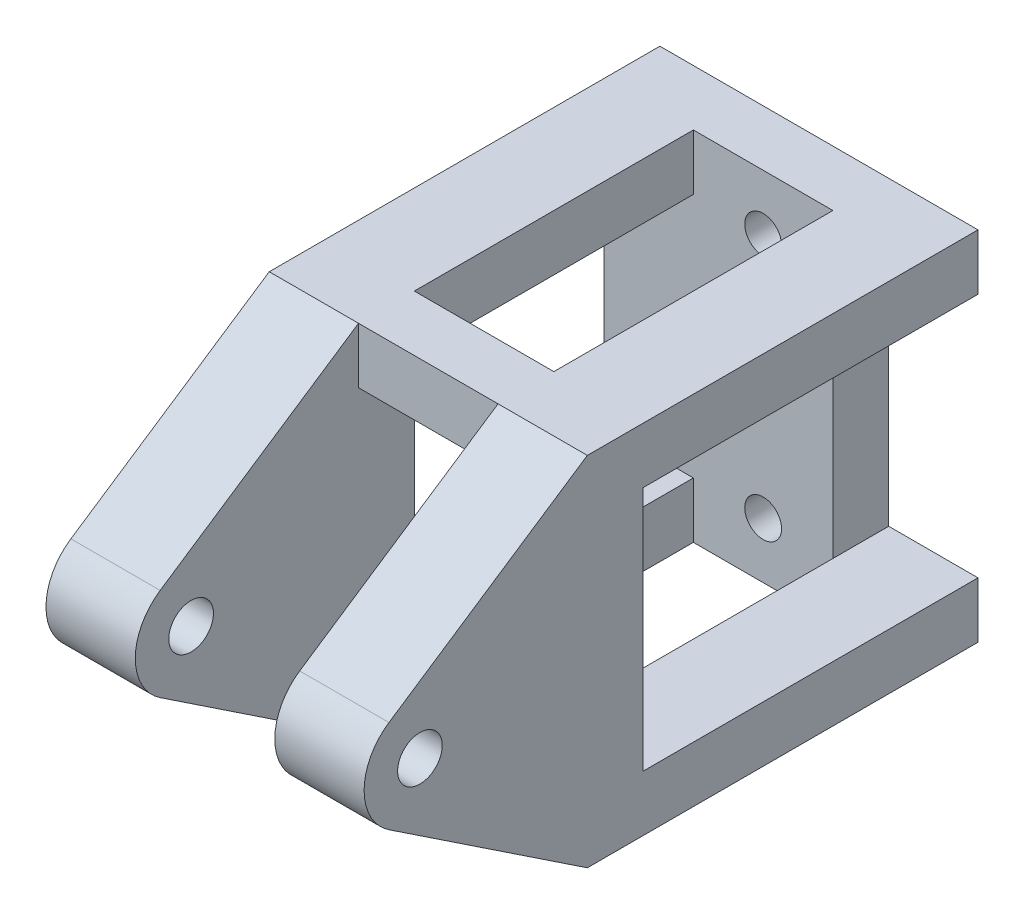
SolidWorks part; units mm, degrees
ref_plane "正面(Front)" through (0, 0, 0) normal (0, 0, 1) x (1, 0, 0)
ref_plane "平面(Top)" through (0, 0, 0) normal (0, 1, 0) x (1, 0, 0)
ref_plane "右側面(Right)" through (0, 0, 0) normal (1, 0, 0) x (0, 0, -1)
sketch "ｽｹｯﾁ1" plane through (0, 0, 0) normal (0, 0, 1) x (1, 0, 0)
  line L1 (-14.25, 16) -> (14.25, 16)
  line L2 (-14.25, 16) -> (-14.25, -16)
  line L3 (-14.25, -16) -> (14.25, -16)
  line L4 (14.25, 16) -> (14.25, -16)
  line L5 (-14.25, 16) -> (14.25, -16) construction
  line L6 (-14.25, -16) -> (14.25, 16) construction
  point P0 (0, 0)
  dimension "D1" = 28.5
  dimension "D2" = 32
extrude "ﾎﾞｽ - 押し出し1" add sketch "ｽｹｯﾁ1" along normal blind 5
sketch "ｽｹｯﾁ3" plane through (14.25, 0, 0) normal (1, 0, 0) x (0, 0, -1)
  line L0 (-5, 16) -> (-35, 16)
  line L1 (-35, 16) -> (-52.772, 4.1613)
  line L2 (0, 0) -> (-92.7849, 0) construction
  line L3 (-5, -16) -> (-5, 16) construction
  line L4 (-35, -16) -> (-52.772, -4.1613)
  line L5 (-5, -16) -> (-35, -16)
  line L6 (-5, -16) -> (-5, 16)
  arc A0 (-52.772, 4.1613) -> (-52.772, -4.1613) centre (-50, 0) ccw
  circle A1 centre (-50, 0) radius 2
  dimension "D2" = 5
  dimension "D4" = 4
  dimension "D1" = 45
  dimension "D3" = 30
extrude "ﾎﾞｽ - 押し出し2" add sketch "ｽｹｯﾁ3" against normal blind 8
mirror "ﾐﾗｰ1" about plane through (0, 0, 0) normal (1, 0, 0) of "ﾎﾞｽ - 押し出し2"
sketch "ｽｹｯﾁ4" plane through (0, 0, 5) normal (0, 0, 1) x (1, 0, 0)
  line L0 (0, 0) -> (26.7416, 0) construction
  line L1 (0, 0) -> (0, 23.9443) construction
  line L2 (6.25, 16) -> (-6.25, 16) construction
  circle A0 centre (0, 11) radius 1.65
  circle A1 centre (0, -11) radius 1.65
  dimension "D1" = 3.3
  dimension "D2" = 5
extrude "ｶｯﾄ - 押し出し1" cut sketch "ｽｹｯﾁ4" against normal through all
sketch "ｽｹｯﾁ5" plane through (0, 0, 0) normal (0, 0, 1) x (1, 0, 0)
  circle A0 centre (12.35, -5) radius 1.75 construction
  circle A1 centre (12.35, -5) radius 1.75 construction
  circle A2 centre (12.35, 5) radius 1.75 construction
  circle A3 centre (12.35, 5) radius 1.75 construction
  circle A4 centre (12.35, -5) radius 1.65
  circle A5 centre (12.35, 5) radius 1.65
  dimension "D1" = 3.3
extrude "ｶｯﾄ - 押し出し2" cut sketch "ｽｹｯﾁ5" along normal blind 5
sketch "ｽｹｯﾁ6" plane through (14.25, 0, 0) normal (1, 0, 0) x (0, 0, -1)
  line L0 (0, 0) -> (-33.2812, 0) construction
  line L1 (-35, 16) -> (0, 16) construction
  line L2 (-30, 11) -> (-5, 11)
  line L3 (-30, 11) -> (-30, -11)
  line L4 (-30, -11) -> (-5, -11)
  line L5 (-5, 11) -> (-5, -11)
  line L6 (-30, 11) -> (-5, -11) construction
  line L7 (-30, -11) -> (-5, 11) construction
  point P3 (-17.5, 0)
  dimension "D1" = 5
  dimension "D2" = 5
  dimension "D3" = 25
extrude "ｶｯﾄ - 押し出し3" cut sketch "ｽｹｯﾁ6" against normal through all
sketch "ｽｹｯﾁ7" plane through (-6.25, 0, 0) normal (1, 0, 0) x (0, 0, -1)
  line L0 (-5, 11) -> (-30, 11) construction
  line L1 (-35, 16) -> (-30, 16)
  line L2 (-35, 16) -> (-35, 11)
  line L3 (-35, 11) -> (-30, 11)
  line L4 (-30, 16) -> (-30, 11)
  line L5 (-30, 11) -> (-30, -11) construction
  line L6 (0, 0) -> (-57.9494, 0) construction
  line L7 (-35, -16) -> (-30, -16)
  line L8 (-35, -16) -> (-35, -11)
  line L9 (-35, -11) -> (-30, -11)
  line L10 (-30, -16) -> (-30, -11)
extrude "ﾎﾞｽ - 押し出し3" add sketch "ｽｹｯﾁ7" along normal up to next
sketch "ｽｹｯﾁ8" plane through (0, 0, 0) normal (0, 0, -1) x (-1, 0, 0)
  line L0 (-14.25, -16) -> (-14.25, 16) construction
  line L1 (-14.25, -11) -> (-6.25, -11)
  line L2 (-14.25, -11) -> (-14.25, 11)
  line L3 (-14.25, 11) -> (-6.25, 11)
  line L4 (-6.25, -11) -> (-6.25, 11)
  dimension "D1" = 8
extrude "ｶｯﾄ - 押し出し4" cut sketch "ｽｹｯﾁ8" against normal blind 10
